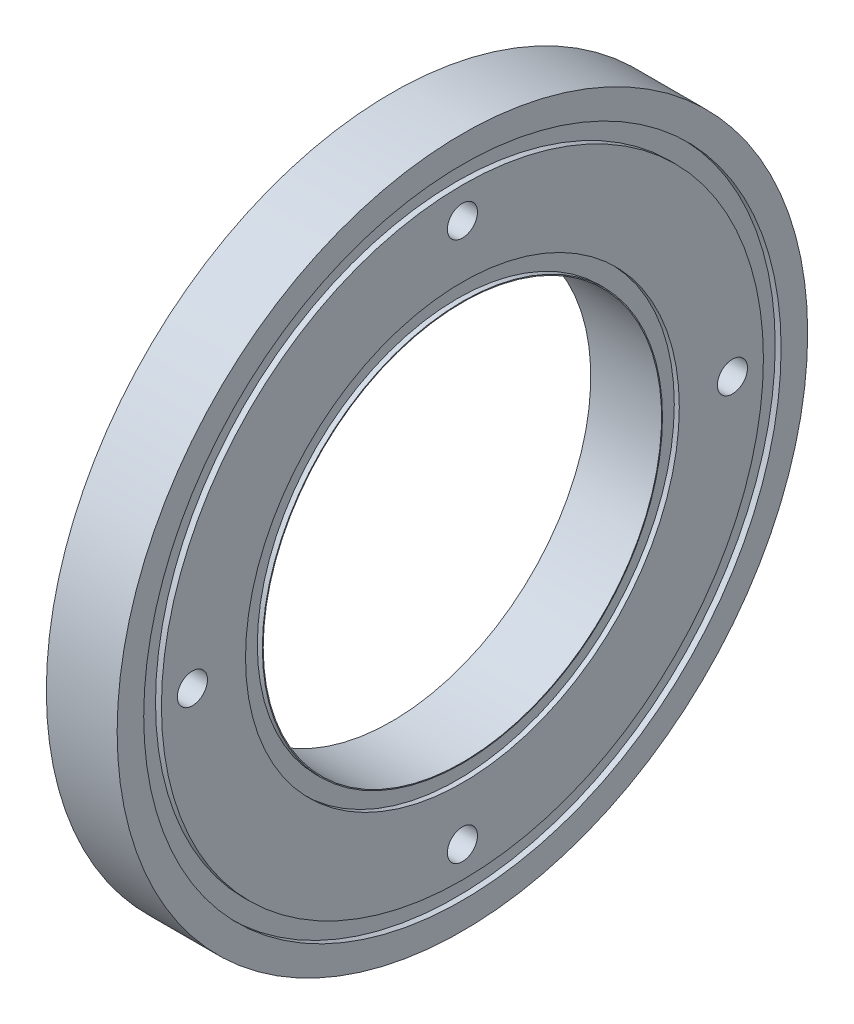
SolidWorks part; units mm, degrees
ref_plane "Front Plane" through (0, 0, 0) normal (0, 0, 1) x (1, 0, 0)
ref_plane "Top Plane" through (0, 0, 0) normal (0, 1, 0) x (1, 0, 0)
ref_plane "Right Plane" through (0, 0, 0) normal (1, 0, 0) x (0, 0, -1)
sketch "Sketch1" plane through (0, 0, 0) normal (0, 0, 1) x (1, 0, 0)
  line L0 (-801.9206, 0) -> (36107.5283, 0) construction
  line L10 (21.0477, 24.5) -> (21.0477, 39)
  line L12 (21.0477, 39) -> (13.0477, 39)
  line L16 (21.0477, 24.5) -> (20.4817, 24.5)
  line L17 (20.4817, 24.5) -> (20.4817, 22.5)
  line L18 (13.0477, 39) -> (13.0477, 24.5)
  line L22 (18.4817, 22.5) -> (20.4817, 22.5)
  line L28 (13.0477, 24.5) -> (13.6137, 24.5)
  line L29 (13.6137, 24.5) -> (13.6137, 22.5)
  line L30 (13.6137, 22.5) -> (18.4817, 22.5)
  line L31 (21.0477, 36) -> (20.3807, 36)
  line L32 (20.3807, 36) -> (20.3807, 34)
  line L33 (20.3807, 34) -> (21.0477, 34)
  line L34 (13.0477, 36) -> (13.7147, 36)
  line L35 (13.7147, 36) -> (13.7147, 34)
  line L36 (13.7147, 34) -> (13.0477, 34)
  line L37 (20.4817, 22.6) -> (21.0477, 22.6)
  line L38 (21.0477, 22.6) -> (21.0477, 22.5)
  line L39 (21.0477, 22.5) -> (20.4817, 22.5)
  line L40 (13.6137, 22.6) -> (13.0477, 22.6)
  line L41 (13.0477, 22.6) -> (13.0477, 22.5)
  line L42 (13.0477, 22.5) -> (13.6137, 22.5)
  dimension "D1" = 8
  dimension "D5" = 39
  dimension "D2" = 36
  dimension "D3" = 0.566
  dimension "D4" = 2
  dimension "D6" = 0.667
  dimension "D7" = 0.1
  dimension "D8" = 24.5
  dimension "D9" = 2
  dimension "D10" = 2
revolve "Revolve17" add sketch "Sketch1" angle 360 about L0 region at (17.0477, 30.7899, 0) region at (20.7647, 22.55, 0) region at (13.3307, 22.55, 0)
sketch "Sketch4" plane through (13.0477, 0, 0) normal (-1, 0, 0) x (0, 0, 1)
  circle A0 centre (0, 0) radius 30.5 construction
  point P3 (0, 30.5)
  point P7 (30.5, 0)
  point P12 (-30.5, 0)
  point P13 (0, -30.5)
  dimension "D1" = 61
hole_wizard "M3 Clearance Hole1" positions "Sketch4" profile "Sketch5" hole size "M3" standard "ISO"
sketch "Sketch5" plane through (13.0477, -30.5, 0) normal (0, 1, 0) x (0, 0, 1)
  line L0 (0, 0) -> (0, 9.0215)
  line L1 (0, 9.0215) -> (1.7, 8)
  line L2 (1.7, 8) -> (1.7, 0)
  line L5 (1.7, 0) -> (0, 0)
  line L10 (0, 9.0215) -> (-1.7, 8) construction
  line L11 (0, -6.35) -> (0, 107.95) construction
  dimension "Hole Dia." = 3.4
  dimension "Hole Depth" = 8
  dimension "Drill Angle" = 118
